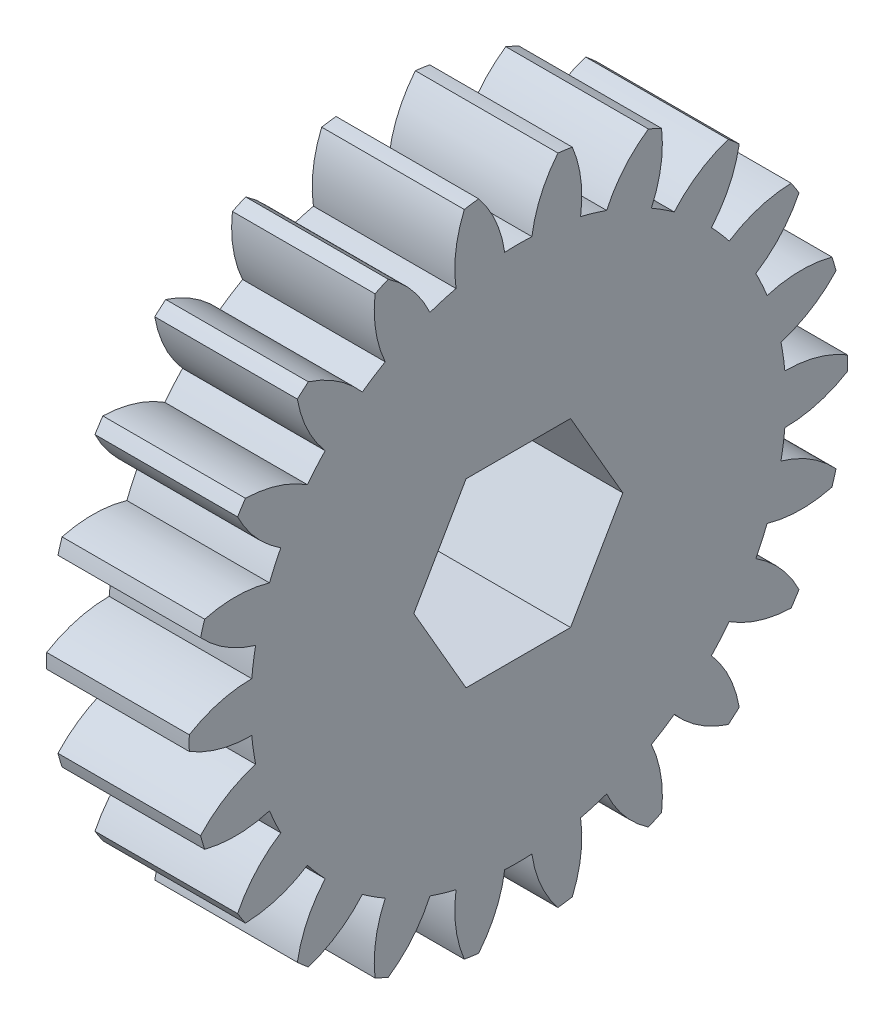
SolidWorks part; units mm, degrees
ref_plane "Plane1" through (0, 0, 0) normal (0, 0, 1) x (1, 0, 0)
ref_plane "Plane2" through (0, 0, 0) normal (0, 1, 0) x (1, 0, 0)
ref_plane "Plane3" through (0, 0, 0) normal (1, 0, 0) x (0, 0, -1)
sketch "HoldingSke" plane through (0, 0, 0) normal (0, 1, 0) x (1, 0, 0)
  line L0 (0, 0) -> (471.0094, -190.3001)
  line L1 (-15, 0) -> (100, 0) construction
  line L2 (0, 0) -> (-2.1039, 2.3779)
  line L3 (0, 0) -> (-11.863, 4.5341)
  line L4 (0, 0) -> (8.0072, 3.2351)
  line L5 (0, 0) -> (-47.5972, -17.7524)
  line L6 (0, 0) -> (-5.4745, -3.6936)
  line L7 (-2.1039, 2.3779) -> (8.8308, 51.9871)
  line L8 (-76.2, 54.61) -> (-75.184, 54.61)
  line L9 (-71.009, 38.7566) -> (-53.1078, 45.2721)
  line L10 (-76.2, 71.12) -> (104.1128, 71.12)
  line L11 (0, 0) -> (-6.604, 0)
  line L12 (-76.2, 101.6) -> (-76.1492, 101.6)
  line L13 (24.9733, 27.94) -> (52.9518, 28.4284)
  line L14 (24.9733, 27.94) -> (25.0241, 27.9398)
  line L15 (24.9733, 27.94) -> (100.4021, 29.52)
  circle A0 centre (0, 0) radius 0.5
  circle A1 centre (0, 0) radius 12.3952
  circle A2 centre (0, 0) radius 38.1
  circle A3 centre (0, 0) radius 0.5
  dimension "Num_teeth" = 22
  dimension "H" = 19.05
  dimension "Pitch_radius" = 180.3128
  dimension "Width" = 6.604
  dimension "Thickness" = 6.604
sketch "BasProSke" plane through (0, 0, 0) normal (0, 1, 0) x (1, 0, 0)
  line L0 (-10, 0) -> (60, 0) construction
  line L1 (0, 0) -> (0, 15.24)
  line L2 (0, 0) -> (6.604, 0)
  line L3 (6.604, 0) -> (6.604, 15.24)
  line L4 (6.604, 15.24) -> (0, 15.24)
  dimension "Thickness" = 6.604
  dimension "Diameter" = 30.48
revolve "Base-Revolve" add sketch "BasProSke" angle 360 about L0
sketch "TooCutSke" plane through (0, 0, 0) normal (1, 0, 0) x (0, 0, -1)
  line L1 (0, 0) -> (0, 107) construction
  line L2 (0, 0) -> (-1.0855, 13.9278) construction
  line L3 (0, 0) -> (-3.9679, 27.5972) construction
  line L4 (-1.0855, 13.9278) -> (-1.9839, 13.7986) construction
  arc A0 (0.6295, 12.3792) -> (-0.6295, 12.3792) centre (0, 0) ccw
  arc A1 (1.855, 15.1523) -> (-1.855, 15.1523) centre (0, 0) ccw
  circle A2 centre (0, 0) radius 13.97 construction
  circle A3 centre (0, 0) radius 13.1275 construction
  arc A4 (-0.6295, 12.3792) -> (-1.855, 15.1523) centre (-6.1617, 11.5916) ccw
  arc A5 (1.855, 15.1523) -> (0.6295, 12.3792) centre (6.1617, 11.5916) ccw
extrude "ToothCut" cut sketch "TooCutSke" along normal through all
fillet "Breaks" [suppressed] radius 0.0254 tangent propagation no
fillet "RootFillets" [suppressed] radius 0.3048
pattern_circular "TeethCuts" count 22 every 16.364 about axis through (-10, 0, 0) along (1, 0, 0) of "ToothCut", "RootFillets", "Breaks"
sketch "HubNeaOneSke" plane through (0, 0, 0) normal (-1, 0, 0) x (0, 0, 1)
  circle A0 centre (0, 0) radius 12.3952
  dimension "Diameter" = 24.7904
extrude "HubNearOne" [suppressed] add sketch "HubNeaOneSke" along normal blind 44.1961
sketch "HubNeaBotSke" plane through (0, 0, 0) normal (-1, 0, 0) x (0, 0, 1)
  circle A0 centre (0, 0) radius 12.3952
  dimension "Diameter" = 24.7904
extrude "HubNearBoth" [suppressed] add sketch "HubNeaBotSke" along normal blind 22.098
ref_plane "FarPln" through (6.604, 0, 0) normal (1, 0, 0) x (0, 0, -1)
sketch "HubFarSke" plane through (6.604, 0, 0) normal (1, 0, 0) x (0, 0, -1)
  circle A0 centre (0, 0) radius 12.3952
  dimension "Diameter" = 24.7904
extrude "HubFar" [suppressed] add sketch "HubFarSke" along normal blind 22.098
sketch "BorSke" plane through (0, 0, 0) normal (1, 0, 0) x (0, 0, -1)
  circle A0 centre (0, 0) radius 0.5
  dimension "Diameter" = 1
extrude "Bore" cut sketch "BorSke" along normal mid plane 101.6001
sketch "KeySke" plane through (0, 0, 0) normal (1, 0, 0) x (0, 0, -1)
  line L0 (-0.127, 0) -> (-0.127, 0.516)
  line L1 (-0.127, 0.516) -> (0.127, 0.516)
  line L2 (0.127, 0.516) -> (0.127, 0)
  line L3 (0, 0) -> (0, 34) construction
  line L4 (-0.127, 0) -> (0.127, 0)
  dimension "Width" = 0.254
extrude "Keyway" [suppressed] cut sketch "KeySke" along normal mid plane 101.6001
pattern_circular "Keyway2" [suppressed] count 2 every 90 about axis through (-10, 0, 0) along (1, 0, 0) reverse direction yes
sketch "Sketch1" plane through (0, 0, 0) normal (-1, 0, 0) x (0, 0, 1)
  circle A0 centre (0, 0) radius 6.985
  dimension "D1" = 13.97
extrude "Boss-Extrude1" add sketch "Sketch1" along normal blind 2.286
sketch "Sketch2" plane through (6.604, 0, 0) normal (1, 0, 0) x (0, 0, -1)
  line L1 (2.4197, 4.191) -> (-2.4197, 4.191)
  line L2 (-2.4197, 4.191) -> (-4.8393, 0)
  line L3 (-4.8393, 0) -> (-2.4197, -4.191)
  line L4 (-2.4197, -4.191) -> (2.4197, -4.191)
  line L5 (2.4197, -4.191) -> (4.8393, 0)
  line L6 (4.8393, 0) -> (2.4197, 4.191)
  circle A0 centre (0, 0) radius 4.191 construction
  dimension "D1" = 8.382
extrude "Cut-Extrude1" cut sketch "Sketch2" against normal through all
chamfer "Chamfer1" distance 0.254 angle 45 1 edges at (-2.286, 0, 6.985)
equation "' \"Pitch@HoldingSke\" = 4"
equation "' \"Num_teeth@HoldingSke\" = 12"
equation "' \"Ap@HoldingSke\" =  20"
equation "' \"Ap@HoldingSke\" = 20"
equation "' \"Width@HoldingSke\" = 0.5"
equation "' \"Hub_dia@HoldingSke\"= 1"
equation "' \"Hub_dia@HoldingSke\" = 1"
equation "' \"Overall_len@HoldingSke\" = 1.0"
equation "' \"Bore@HoldingSke\" = 0.75"
equation "' \"T_dim@HoldingSke\" = 0.85"
equation "' \"Width@KeySke\" = 0.25"
equation "' \"Show_teeth@HoldingSke\" = 13"
equation "' \"Backlash@HoldingSke\" = 0.009"
equation "' \"Addendum_fac@HoldingSke\" = 1.0"
equation "' \"Dedendum_fac@HoldingSke\" = 1.25"
equation "' \"Dedendum_add@HoldingSke\" = 0.00005"
equation "' \"Clearance_fac@HoldingSke\" = 0.25"
equation "' \"Pitch@HoldingSke\" = 0.5"
equation "' \"Num_teeth@HoldingSke\" = 23"
equation "' \"Show_teeth@HoldingSke\" = 23"
equation "' \"Backlash@HoldingSke\" = 0.0375"
equation "\"Overcut_dia@TooCutSke\" = (\"Num_teeth@HoldingSke\" + 2 * \"Addendum_fac@HoldingSke\") / \"Pitch@HoldingSke\" + 0.002"
equation "\"Pitch_dia@TooCutSke\" = \"Num_teeth@HoldingSke\" / \"Pitch@HoldingSke\""
equation "\"Base_dia@TooCutSke\" = \"Num_teeth@HoldingSke\" / \"Pitch@HoldingSke\" * cos((\"Ap@HoldingSke\"  * 3.14159265 / 180))"
equation "\"Root_dia@TooCutSke\" = (\"Num_teeth@HoldingSke\" + 2) / \"Pitch@HoldingSke\" - 2 * (\"Addendum_fac@HoldingSke\" + \"Dedendum_fac@HoldingSke\") / \"Pitch@HoldingSke\" - \"Dedendum_add@HoldingSke\" * 2"
equation "\"Half_ang@TooCutSke\" = 180 / \"Num_teeth@HoldingSke\""
equation "\"Half_CT@TooCutSke\" = \"Num_teeth@HoldingSke\" / \"Pitch@HoldingSke\" * sin((3.14159265 / 2 / \"Num_teeth@HoldingSke\")) / 2 - 7 * \"Backlash@HoldingSke\" / 4"
equation "\"Flank_rad@TooCutSke\" = \"Num_teeth@HoldingSke\" / \"Pitch@HoldingSke\" / 5"
equation "\"Radius@RootFillets\" = \"Clearance_fac@HoldingSke\" / \"Pitch@HoldingSke\" + \"Dedendum_add@HoldingSke\""
equation "\"Break_rad@Breaks\" = 0.02 / \"Pitch@HoldingSke\""
equation "\"Thickness@HoldingSke\" = \"Width@HoldingSke\""
equation "\"OAL@HoldingSke\" = \"Thickness@HoldingSke\""
equation "\"MHD@HoldingSke\" = (\"Num_teeth@HoldingSke\" + 2) / \"Pitch@HoldingSke\" - 2 * (\"Addendum_fac@HoldingSke\" + \"Dedendum_fac@HoldingSke\")  / \"Pitch@HoldingSke\" - \"Dedendum_add@HoldingSke\" * 2"
equation "\"MBD@HoldingSke\" = (\"Num_teeth@HoldingSke\" + 2) / \"Pitch@HoldingSke\" - 2 * (\"Addendum_fac@HoldingSke\" + \"Dedendum_fac@HoldingSke\")  / \"Pitch@HoldingSke\" - \"Dedendum_add@HoldingSke\" * 2 - 0.002"
equation "\"MHD@HoldingSke\" = ((sgn( \"MHD@HoldingSke\" - \"Hub_dia@HoldingSke\" )-1)*( \"MHD@HoldingSke\" - \"Hub_dia@HoldingSke\" ))/-2+ \"Hub_dia@HoldingSke\""
equation "\"MBD@HoldingSke\" = ((sgn( \"MBD@HoldingSke\" - \"Bore@HoldingSke\" )-1)*( \"MBD@HoldingSke\" - \"Bore@HoldingSke\" ))/-2+ \"Bore@HoldingSke\""
equation "\"OAL@HoldingSke\" = ((sgn( \"OAL@HoldingSke\" - \"Overall_len@HoldingSke\" )+1)*( \"OAL@HoldingSke\" - \"Overall_len@HoldingSke\" ))/2 + \"Overall_len@HoldingSke\" + 0.000002"
equation "\"Num_teeth@TeethCuts\" = int( \"Show_teeth@HoldingSke\" ) + 1"
equation "\"Num_teeth@TeethCuts\" = ((sgn( \"Num_teeth@TeethCuts\" - \"Num_teeth@HoldingSke\" )-1)*( \"Num_teeth@TeethCuts\" - \"Num_teeth@HoldingSke\" ))/-2+ \"Num_teeth@HoldingSke\""
equation "\"Num_teeth@TeethCuts\" = ((sgn( \"Num_teeth@TeethCuts\" - 2.0)+1)*( \"Num_teeth@TeethCuts\" - 2.0))/2 +2.0"
equation "\"Angle@TeethCuts\" = 360.0 / \"Num_teeth@HoldingSke\""
equation "\"Diameter@BasProSke\" = (\"Num_teeth@HoldingSke\" + 2 * \"Addendum_fac@HoldingSke\") / \"Pitch@HoldingSke\""
equation "\"Thickness@BasProSke\"  = \"Thickness@HoldingSke\""
equation "' \"Fillet_rad@BasProSke\" =  \"Thickness@HoldingSke\" * 0.05"
equation "' \"Fillet_rad@BasProSke\" = \"Thickness@HoldingSke\" * 0.05"
equation "\"MHD@HoldingSke\" = ((sgn( \"MHD@HoldingSke\" - \"Root_dia@TooCutSke\" )-1)*( \"MHD@HoldingSke\" - \"Root_dia@TooCutSke\" ))/-2+ \"Root_dia@TooCutSke\""
equation "\"Diameter@HubNeaOneSke\" = \"MHD@HoldingSke\""
equation "\"Length@HubNearOne\" = \"OAL@HoldingSke\" - \"Thickness@BasProSke\""
equation "\"Diameter@HubNeaBotSke\" = \"MHD@HoldingSke\""
equation "\"Length@HubNearBoth\" = ( \"OAL@HoldingSke\" - \"Thickness@BasProSke\" ) / 2.0"
equation "\"Thickness@FarPln\" = \"Thickness@BasProSke\""
equation "\"Diameter@HubFarSke\" = \"MHD@HoldingSke\""
equation "\"Length@HubFar\" = ( \"OAL@HoldingSke\" - \"Thickness@BasProSke\" ) / 2.0"
equation "\"Diameter@BorSke\" = \"MBD@HoldingSke\""
equation "\"D1@Bore\" = \"OAL@HoldingSke\" * 2.0"
equation "\"D1@Keyway\" = \"OAL@HoldingSke\" * 2.0"
equation "\"Offset@KeySke\" = \"T_dim@HoldingSke\" - \"MBD@HoldingSke\" / 2.0"
